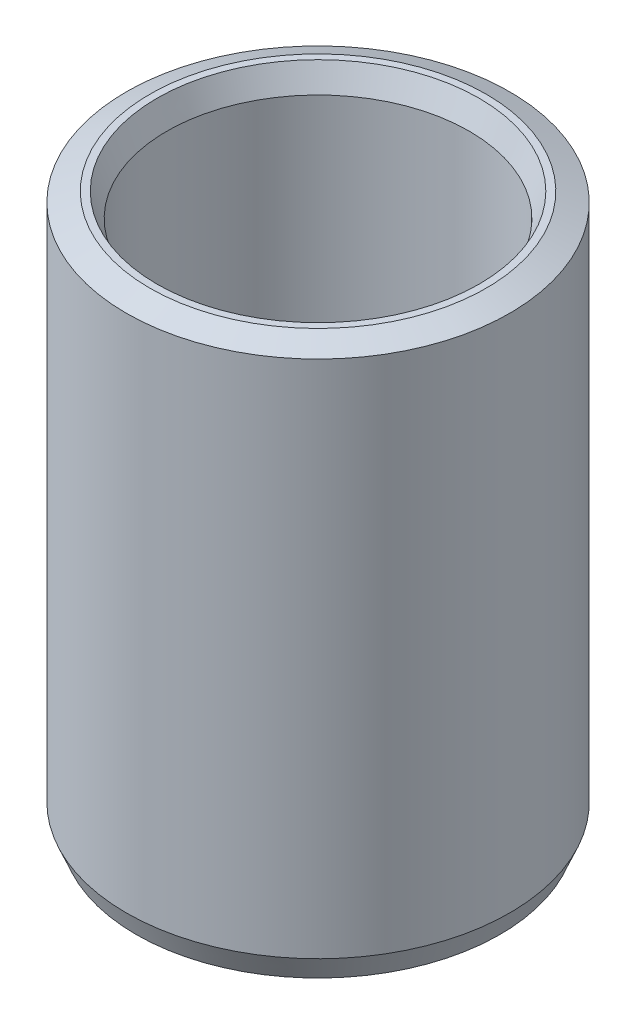
SolidWorks part; units mm, degrees
ref_plane "Front Plane" through (0, 0, 0) normal (0, 0, 1) x (1, 0, 0)
ref_plane "Top Plane" through (0, 0, 0) normal (0, 1, 0) x (1, 0, 0)
ref_plane "Right Plane" through (0, 0, 0) normal (1, 0, 0) x (0, 0, -1)
sketch "Sketch1" plane through (0, 0, 0) normal (0, 1, 0) x (1, 0, 0)
  circle A0 centre (0, 0) radius 47.5
  dimension "SLEEVE_OD" = 95
extrude "Boss-Extrude1" add sketch "Sketch1" along normal blind 136.923
sketch "Sketch2" plane through (0, 0, 0) normal (0, 1, 0) x (1, 0, 0)
  circle A0 centre (0, 0) radius 37.4639
  dimension "BORE_D" = 74.9279
extrude "Cut-Extrude1" cut sketch "Sketch2" along normal through all
chamfer "Chamfer1" distance 2.4311 angle 67.456 4 edges at (0, 136.923, 37.4639) (0, 0, 37.4639) (0, 0, 47.5) (0, 136.923, 47.5) first distance on face at (0, 136.923, 37.4639) first distance on face at (0, 0, 37.4639) first distance on face at (0, 136.923, 47.5)
